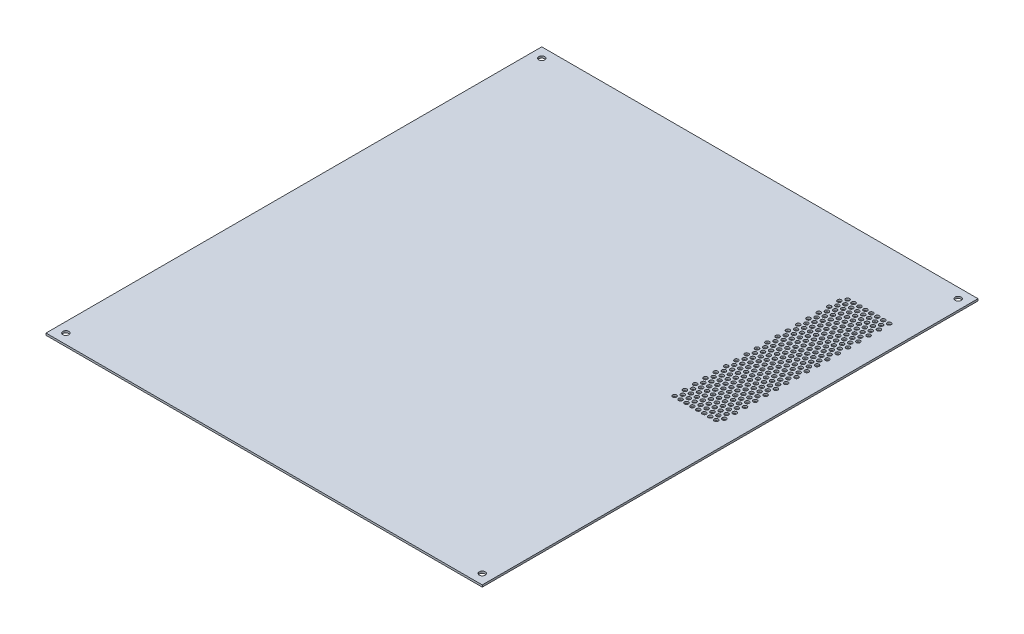
SolidWorks part; units mm, degrees
ref_plane "Front Plane" through (0, 0, 0) normal (0, 0, 1) x (1, 0, 0)
ref_plane "Top Plane" through (0, 0, 0) normal (0, 1, 0) x (1, 0, 0)
ref_plane "Right Plane" through (0, 0, 0) normal (1, 0, 0) x (0, 0, -1)
sketch "Sketch1" plane through (0, 0, 0) normal (0, 1, 0) x (1, 0, 0)
  line L0 (20, 20) -> (20, 480) construction
  line L1 (0, 0) -> (440, 0)
  line L2 (0, 0) -> (0, 500)
  line L3 (0, 500) -> (440, 500)
  line L4 (440, 0) -> (440, 500)
  line L5 (20, 480) -> (420, 480) construction
  line L6 (420, 20) -> (420, 480) construction
  line L7 (20, 20) -> (420, 20) construction
  line L9 (420, 440) -> (370, 440) construction
  line L10 (420, 440) -> (420, 260) construction
  line L11 (420, 260) -> (370, 260) construction
  line L12 (370, 440) -> (370, 260) construction
  circle A0 centre (372, 262) radius 2
  circle A1 centre (375, 267.1962) radius 2
  circle A2 centre (381, 267.1962) radius 2
  circle A3 centre (378, 262) radius 2
  circle A4 centre (387, 267.1962) radius 2
  circle A5 centre (384, 262) radius 2
  circle A6 centre (393, 267.1962) radius 2
  circle A7 centre (390, 262) radius 2
  circle A8 centre (399, 267.1962) radius 2
  circle A9 centre (396, 262) radius 2
  circle A10 centre (405, 267.1962) radius 2
  circle A11 centre (402, 262) radius 2
  circle A12 centre (411, 267.1962) radius 2
  circle A13 centre (408, 262) radius 2
  circle A14 centre (417, 267.1962) radius 2
  circle A15 centre (414, 262) radius 2
  circle A16 centre (381, 277.5862) radius 2
  circle A17 centre (378, 272.39) radius 2
  circle A18 centre (387, 277.5862) radius 2
  circle A19 centre (384, 272.39) radius 2
  circle A20 centre (393, 277.5862) radius 2
  circle A21 centre (390, 272.39) radius 2
  circle A22 centre (399, 277.5862) radius 2
  circle A23 centre (396, 272.39) radius 2
  circle A24 centre (405, 277.5862) radius 2
  circle A25 centre (402, 272.39) radius 2
  circle A26 centre (411, 277.5862) radius 2
  circle A27 centre (408, 272.39) radius 2
  circle A28 centre (417, 277.5862) radius 2
  circle A29 centre (414, 272.39) radius 2
  circle A30 centre (381, 287.9762) radius 2
  circle A31 centre (378, 282.78) radius 2
  circle A32 centre (387, 287.9762) radius 2
  circle A33 centre (384, 282.78) radius 2
  circle A34 centre (393, 287.9762) radius 2
  circle A35 centre (390, 282.78) radius 2
  circle A36 centre (399, 287.9762) radius 2
  circle A37 centre (396, 282.78) radius 2
  circle A38 centre (405, 287.9762) radius 2
  circle A39 centre (402, 282.78) radius 2
  circle A40 centre (411, 287.9762) radius 2
  circle A41 centre (408, 282.78) radius 2
  circle A42 centre (417, 287.9762) radius 2
  circle A43 centre (414, 282.78) radius 2
  circle A44 centre (381, 298.3662) radius 2
  circle A45 centre (378, 293.17) radius 2
  circle A46 centre (387, 298.3662) radius 2
  circle A47 centre (384, 293.17) radius 2
  circle A48 centre (393, 298.3662) radius 2
  circle A49 centre (390, 293.17) radius 2
  circle A50 centre (399, 298.3662) radius 2
  circle A51 centre (396, 293.17) radius 2
  circle A52 centre (405, 298.3662) radius 2
  circle A53 centre (402, 293.17) radius 2
  circle A54 centre (411, 298.3662) radius 2
  circle A55 centre (408, 293.17) radius 2
  circle A56 centre (417, 298.3662) radius 2
  circle A57 centre (414, 293.17) radius 2
  circle A58 centre (381, 308.7562) radius 2
  circle A59 centre (378, 303.56) radius 2
  circle A60 centre (387, 308.7562) radius 2
  circle A61 centre (384, 303.56) radius 2
  circle A62 centre (393, 308.7562) radius 2
  circle A63 centre (390, 303.56) radius 2
  circle A64 centre (399, 308.7562) radius 2
  circle A65 centre (396, 303.56) radius 2
  circle A66 centre (405, 308.7562) radius 2
  circle A67 centre (402, 303.56) radius 2
  circle A68 centre (411, 308.7562) radius 2
  circle A69 centre (408, 303.56) radius 2
  circle A70 centre (417, 308.7562) radius 2
  circle A71 centre (414, 303.56) radius 2
  circle A72 centre (381, 319.1462) radius 2
  circle A73 centre (378, 313.95) radius 2
  circle A74 centre (387, 319.1462) radius 2
  circle A75 centre (384, 313.95) radius 2
  circle A76 centre (393, 319.1462) radius 2
  circle A77 centre (390, 313.95) radius 2
  circle A78 centre (399, 319.1462) radius 2
  circle A79 centre (396, 313.95) radius 2
  circle A80 centre (405, 319.1462) radius 2
  circle A81 centre (402, 313.95) radius 2
  circle A82 centre (411, 319.1462) radius 2
  circle A83 centre (408, 313.95) radius 2
  circle A84 centre (417, 319.1462) radius 2
  circle A85 centre (414, 313.95) radius 2
  circle A86 centre (381, 329.5362) radius 2
  circle A87 centre (378, 324.34) radius 2
  circle A88 centre (387, 329.5362) radius 2
  circle A89 centre (384, 324.34) radius 2
  circle A90 centre (393, 329.5362) radius 2
  circle A91 centre (390, 324.34) radius 2
  circle A92 centre (399, 329.5362) radius 2
  circle A93 centre (396, 324.34) radius 2
  circle A94 centre (405, 329.5362) radius 2
  circle A95 centre (402, 324.34) radius 2
  circle A96 centre (411, 329.5362) radius 2
  circle A97 centre (408, 324.34) radius 2
  circle A98 centre (417, 329.5362) radius 2
  circle A99 centre (414, 324.34) radius 2
  circle A100 centre (381, 339.9262) radius 2
  circle A101 centre (378, 334.73) radius 2
  circle A102 centre (387, 339.9262) radius 2
  circle A103 centre (384, 334.73) radius 2
  circle A104 centre (393, 339.9262) radius 2
  circle A105 centre (390, 334.73) radius 2
  circle A106 centre (399, 339.9262) radius 2
  circle A107 centre (396, 334.73) radius 2
  circle A108 centre (405, 339.9262) radius 2
  circle A109 centre (402, 334.73) radius 2
  circle A110 centre (411, 339.9262) radius 2
  circle A111 centre (408, 334.73) radius 2
  circle A112 centre (417, 339.9262) radius 2
  circle A113 centre (414, 334.73) radius 2
  circle A114 centre (381, 350.3162) radius 2
  circle A115 centre (378, 345.12) radius 2
  circle A116 centre (387, 350.3162) radius 2
  circle A117 centre (384, 345.12) radius 2
  circle A118 centre (393, 350.3162) radius 2
  circle A119 centre (390, 345.12) radius 2
  circle A120 centre (399, 350.3162) radius 2
  circle A121 centre (396, 345.12) radius 2
  circle A122 centre (405, 350.3162) radius 2
  circle A123 centre (402, 345.12) radius 2
  circle A124 centre (411, 350.3162) radius 2
  circle A125 centre (408, 345.12) radius 2
  circle A126 centre (417, 350.3162) radius 2
  circle A127 centre (414, 345.12) radius 2
  circle A128 centre (381, 360.7062) radius 2
  circle A129 centre (378, 355.51) radius 2
  circle A130 centre (387, 360.7062) radius 2
  circle A131 centre (384, 355.51) radius 2
  circle A132 centre (393, 360.7062) radius 2
  circle A133 centre (390, 355.51) radius 2
  circle A134 centre (399, 360.7062) radius 2
  circle A135 centre (396, 355.51) radius 2
  circle A136 centre (405, 360.7062) radius 2
  circle A137 centre (402, 355.51) radius 2
  circle A138 centre (411, 360.7062) radius 2
  circle A139 centre (408, 355.51) radius 2
  circle A140 centre (417, 360.7062) radius 2
  circle A141 centre (414, 355.51) radius 2
  circle A142 centre (381, 371.0962) radius 2
  circle A143 centre (378, 365.9) radius 2
  circle A144 centre (387, 371.0962) radius 2
  circle A145 centre (384, 365.9) radius 2
  circle A146 centre (393, 371.0962) radius 2
  circle A147 centre (390, 365.9) radius 2
  circle A148 centre (399, 371.0962) radius 2
  circle A149 centre (396, 365.9) radius 2
  circle A150 centre (405, 371.0962) radius 2
  circle A151 centre (402, 365.9) radius 2
  circle A152 centre (411, 371.0962) radius 2
  circle A153 centre (408, 365.9) radius 2
  circle A154 centre (417, 371.0962) radius 2
  circle A155 centre (414, 365.9) radius 2
  circle A156 centre (381, 381.4862) radius 2
  circle A157 centre (378, 376.29) radius 2
  circle A158 centre (387, 381.4862) radius 2
  circle A159 centre (384, 376.29) radius 2
  circle A160 centre (393, 381.4862) radius 2
  circle A161 centre (390, 376.29) radius 2
  circle A162 centre (399, 381.4862) radius 2
  circle A163 centre (396, 376.29) radius 2
  circle A164 centre (405, 381.4862) radius 2
  circle A165 centre (402, 376.29) radius 2
  circle A166 centre (411, 381.4862) radius 2
  circle A167 centre (408, 376.29) radius 2
  circle A168 centre (417, 381.4862) radius 2
  circle A169 centre (414, 376.29) radius 2
  circle A170 centre (381, 391.8762) radius 2
  circle A171 centre (378, 386.68) radius 2
  circle A172 centre (387, 391.8762) radius 2
  circle A173 centre (384, 386.68) radius 2
  circle A174 centre (393, 391.8762) radius 2
  circle A175 centre (390, 386.68) radius 2
  circle A176 centre (399, 391.8762) radius 2
  circle A177 centre (396, 386.68) radius 2
  circle A178 centre (405, 391.8762) radius 2
  circle A179 centre (402, 386.68) radius 2
  circle A180 centre (411, 391.8762) radius 2
  circle A181 centre (408, 386.68) radius 2
  circle A182 centre (417, 391.8762) radius 2
  circle A183 centre (414, 386.68) radius 2
  circle A184 centre (381, 402.2662) radius 2
  circle A185 centre (378, 397.07) radius 2
  circle A186 centre (387, 402.2662) radius 2
  circle A187 centre (384, 397.07) radius 2
  circle A188 centre (393, 402.2662) radius 2
  circle A189 centre (390, 397.07) radius 2
  circle A190 centre (399, 402.2662) radius 2
  circle A191 centre (396, 397.07) radius 2
  circle A192 centre (405, 402.2662) radius 2
  circle A193 centre (402, 397.07) radius 2
  circle A194 centre (411, 402.2662) radius 2
  circle A195 centre (408, 397.07) radius 2
  circle A196 centre (417, 402.2662) radius 2
  circle A197 centre (414, 397.07) radius 2
  circle A198 centre (381, 412.6562) radius 2
  circle A199 centre (378, 407.46) radius 2
  circle A200 centre (387, 412.6562) radius 2
  circle A201 centre (384, 407.46) radius 2
  circle A202 centre (393, 412.6562) radius 2
  circle A203 centre (390, 407.46) radius 2
  circle A204 centre (399, 412.6562) radius 2
  circle A205 centre (396, 407.46) radius 2
  circle A206 centre (405, 412.6562) radius 2
  circle A207 centre (402, 407.46) radius 2
  circle A208 centre (411, 412.6562) radius 2
  circle A209 centre (408, 407.46) radius 2
  circle A210 centre (417, 412.6562) radius 2
  circle A211 centre (414, 407.46) radius 2
  circle A212 centre (381, 423.0462) radius 2
  circle A213 centre (378, 417.85) radius 2
  circle A214 centre (387, 423.0462) radius 2
  circle A215 centre (384, 417.85) radius 2
  circle A216 centre (393, 423.0462) radius 2
  circle A217 centre (390, 417.85) radius 2
  circle A218 centre (399, 423.0462) radius 2
  circle A219 centre (396, 417.85) radius 2
  circle A220 centre (405, 423.0462) radius 2
  circle A221 centre (402, 417.85) radius 2
  circle A222 centre (411, 423.0462) radius 2
  circle A223 centre (408, 417.85) radius 2
  circle A224 centre (417, 423.0462) radius 2
  circle A225 centre (414, 417.85) radius 2
  circle A226 centre (381, 433.4362) radius 2
  circle A227 centre (378, 428.24) radius 2
  circle A228 centre (387, 433.4362) radius 2
  circle A229 centre (384, 428.24) radius 2
  circle A230 centre (393, 433.4362) radius 2
  circle A231 centre (390, 428.24) radius 2
  circle A232 centre (399, 433.4362) radius 2
  circle A233 centre (396, 428.24) radius 2
  circle A234 centre (405, 433.4362) radius 2
  circle A235 centre (402, 428.24) radius 2
  circle A236 centre (411, 433.4362) radius 2
  circle A237 centre (408, 428.24) radius 2
  circle A238 centre (417, 433.4362) radius 2
  circle A239 centre (414, 428.24) radius 2
  circle A240 centre (375, 277.5862) radius 2
  circle A241 centre (372, 272.39) radius 2
  circle A242 centre (375, 287.9762) radius 2
  circle A243 centre (372, 282.78) radius 2
  circle A244 centre (375, 298.3662) radius 2
  circle A245 centre (372, 293.17) radius 2
  circle A246 centre (375, 308.7562) radius 2
  circle A247 centre (372, 303.56) radius 2
  circle A248 centre (375, 319.1462) radius 2
  circle A249 centre (372, 313.95) radius 2
  circle A250 centre (375, 329.5362) radius 2
  circle A251 centre (372, 324.34) radius 2
  circle A252 centre (375, 339.9262) radius 2
  circle A253 centre (372, 334.73) radius 2
  circle A254 centre (375, 350.3162) radius 2
  circle A255 centre (372, 345.12) radius 2
  circle A256 centre (375, 360.7062) radius 2
  circle A257 centre (372, 355.51) radius 2
  circle A258 centre (375, 371.0962) radius 2
  circle A259 centre (372, 365.9) radius 2
  circle A260 centre (375, 381.4862) radius 2
  circle A261 centre (372, 376.29) radius 2
  circle A262 centre (375, 391.8762) radius 2
  circle A263 centre (372, 386.68) radius 2
  circle A264 centre (375, 402.2662) radius 2
  circle A265 centre (372, 397.07) radius 2
  circle A266 centre (375, 412.6562) radius 2
  circle A267 centre (372, 407.46) radius 2
  circle A268 centre (375, 423.0462) radius 2
  circle A269 centre (372, 417.85) radius 2
  circle A270 centre (375, 433.4362) radius 2
  circle A271 centre (372, 428.24) radius 2
  circle A272 centre (10, 490) radius 3
  circle A273 centre (430, 490) radius 3
  circle A274 centre (430, 10) radius 3
  circle A275 centre (10, 10) radius 3
  dimension "D7" = 2
  dimension "D8" = 2
  dimension "D12" = 10
  dimension "D14" = 10
  dimension "D21" = 6
  dimension "D22" = 4
  dimension "D2" = 180
  dimension "D3" = 50
  dimension "D4" = 60
  dimension "D5" = 500
  dimension "D6" = 440
  dimension "D9" = 8
  dimension "D10" = 17
  dimension "D11" = 6
  dimension "D13" = 5.1962
  dimension "D15" = 10
  dimension "D16" = 10
  dimension "D17" = 10
  dimension "D18" = 10
  dimension "D19" = 10
  dimension "D20" = 10
  dimension "D1" = 20
extrude "Boss-Extrude1" add sketch "Sketch1" along normal blind 2
